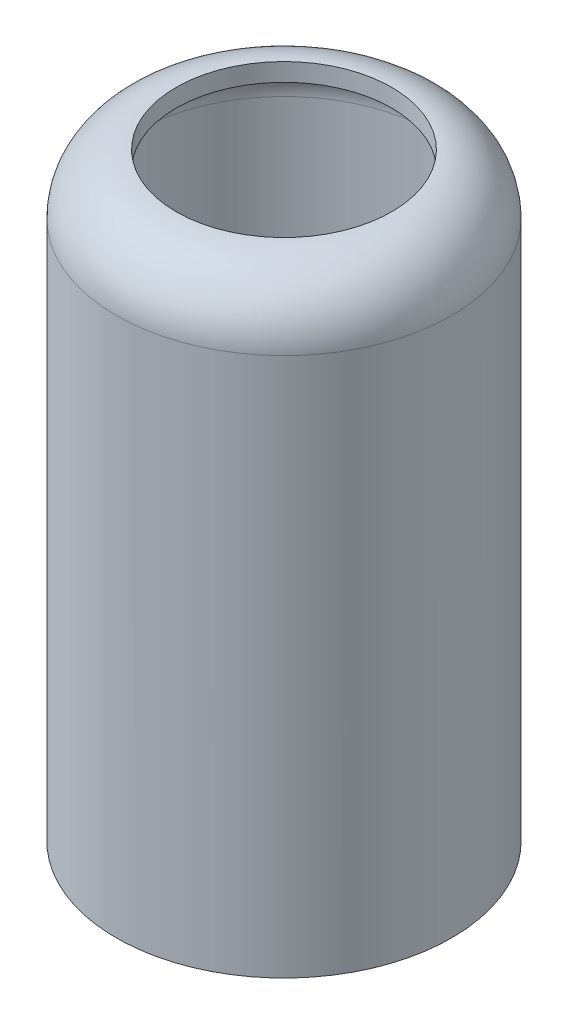
SolidWorks part; units mm, degrees
ref_plane "Front Plane" through (0, 0, 0) normal (0, 0, 1) x (1, 0, 0)
ref_plane "Top Plane" through (0, 0, 0) normal (0, 1, 0) x (1, 0, 0)
ref_plane "Right Plane" through (0, 0, 0) normal (1, 0, 0) x (0, 0, -1)
sketch "Sketch1" plane through (0, 0, 0) normal (0, 1, 0) x (1, 0, 0)
  circle A0 centre (0, 0) radius 28
  dimension "D1" = 56
extrude "Boss-Extrude1" add sketch "Sketch1" along normal blind 100
fillet "Fillet1" radius 10 1 edges at (0, 100, 28)
shell "Shell1" thickness 3 removed face at (0, 100, 18)
